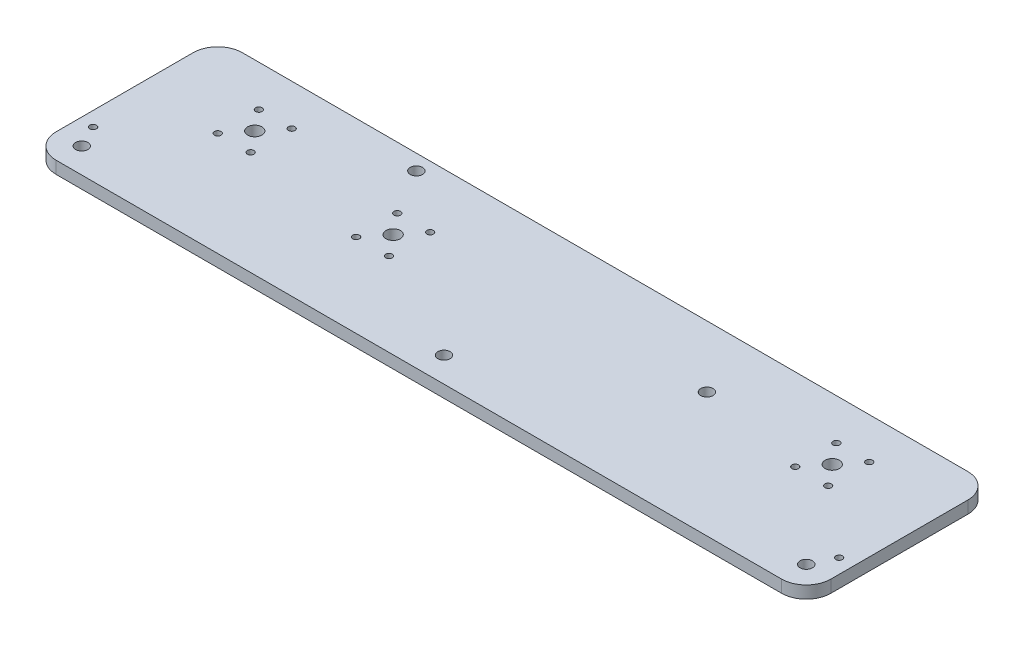
SolidWorks part; units mm, degrees
material "Policarbonato"
ref_plane "Plano frontal" through (0, 0, 0) normal (0, 0, 1) x (1, 0, 0)
ref_plane "Plano superior" through (0, 0, 0) normal (0, 1, 0) x (1, 0, 0)
ref_plane "Plano direito" through (0, 0, 0) normal (1, 0, 0) x (0, 0, -1)
sketch "Esboço1" plane through (0, 0, 0) normal (0, 1, 0) x (1, 0, 0)
  line L4 (132.965, 0) -> (148.965, 0) construction
  line L6 (188.965, -38.6487) -> (188.965, 28)
  line L7 (176.965, 40) -> (-176.0908, 40)
  line L8 (-188.0908, 28) -> (-188.0908, -38.6487)
  line L9 (132.965, 0) -> (132.965, 20) construction
  line L11 (132.965, 20) -> (148.965, 20) construction
  line L12 (148.965, 0) -> (148.965, 20) construction
  line L13 (132.965, 0) -> (148.965, 20) construction
  line L14 (132.965, 20) -> (148.965, 0) construction
  line L15 (-148.0908, 0) -> (-132.0908, 0) construction
  line L16 (-148.0908, 0) -> (-148.0908, 20) construction
  line L17 (-148.0908, 20) -> (-132.0908, 20) construction
  line L18 (-132.0908, 0) -> (-132.0908, 20) construction
  line L19 (-176.0908, -50.6487) -> (176.965, -50.6487)
  line L20 (-148.0908, 0) -> (-132.0908, 20) construction
  line L21 (-148.0908, 20) -> (-132.0908, 0) construction
  line L22 (-70.7345, -10) -> (-54.7345, -10) construction
  line L23 (-70.7345, -10) -> (-70.7345, 10) construction
  line L24 (-70.7345, 10) -> (-54.7345, 10) construction
  line L25 (-54.7345, -10) -> (-54.7345, 10) construction
  line L26 (-70.7345, -10) -> (-54.7345, 10) construction
  line L27 (-70.7345, 10) -> (-54.7345, -10) construction
  arc A0 (176.965, -50.6487) -> (188.965, -38.6487) centre (176.965, -38.6487) ccw
  arc A1 (188.965, 28) -> (176.965, 40) centre (176.965, 28) ccw
  arc A2 (-188.0908, 28) -> (-176.0908, 40) centre (-176.0908, 28) cw
  arc A3 (-188.0908, -38.6487) -> (-176.0908, -50.6487) centre (-176.0908, -38.6487) ccw
  circle A7 centre (-62.7345, 0) radius 3.5
  circle A8 centre (176.7481, -38.4318) radius 3
  circle A9 centre (0.4371, -38.4318) radius 3
  circle A10 centre (79.965, 10) radius 3
  circle A11 centre (-140.0908, 10) radius 3.5
  circle A13 centre (-148.0908, 0) radius 1.6
  circle A14 centre (-132.0908, 0) radius 1.6
  circle A15 centre (-132.0908, 20) radius 1.6
  circle A16 centre (-148.0908, 20) radius 1.6
  circle A17 centre (-70.7345, -10) radius 1.6
  circle A18 centre (-70.7345, 10) radius 1.6
  circle A19 centre (-54.7345, 10) radius 1.6
  circle A20 centre (-54.7345, -10) radius 1.6
  circle A21 centre (-62.7345, 0) radius 25 construction
  circle A22 centre (-83.9303, 32.5) radius 7.5 construction
  circle A23 centre (-140.0908, 10) radius 48 construction
  circle A24 centre (-83.9303, 32.5) radius 3
  circle A25 centre (-175.8739, -38.4318) radius 3
  circle A26 centre (140.965, 10) radius 3.5
  circle A27 centre (148.965, 0) radius 1.6
  circle A28 centre (148.965, 20) radius 1.6
  circle A29 centre (132.965, 0) radius 1.6
  circle A30 centre (132.965, 20) radius 1.6
  circle A33 centre (-181.0908, -27.6487) radius 1.6
  circle A34 centre (181.965, -27.6487) radius 1.6
  point P33 (0.4371, 40)
  dimension "D2" = 377.0558
  dimension "D4" = 7
  dimension "D6" = 12.2169
  dimension "D8" = 203.9448
  dimension "D10" = 48
  dimension "D12" = 16
  dimension "D15" = 20
  dimension "D17" = 6
  dimension "D1" = 12
  dimension "D7" = 40
  dimension "D9" = 30
  dimension "D11" = 7
  dimension "D16" = 3.2
  dimension "D20" = 3.2
  dimension "D25" = 56.1605
  dimension "D26" = 61
  dimension "D27" = 50
  dimension "D28" = 15
  dimension "D29" = 96
  dimension "D3" = 90.6487
  dimension "D5" = 12.2169
  dimension "D13" = 16
  dimension "D14" = 20
  dimension "D18" = 12.2169
  dimension "D19" = 30
  dimension "D21" = 16
  dimension "D22" = 20
  dimension "D23" = 48
  dimension "D24" = 7.5
  dimension "D30" = 7
  dimension "D31" = 7
  dimension "D32" = 23
extrude "Ressalto-extrusão1" add sketch "Esboço1" against normal blind 6
